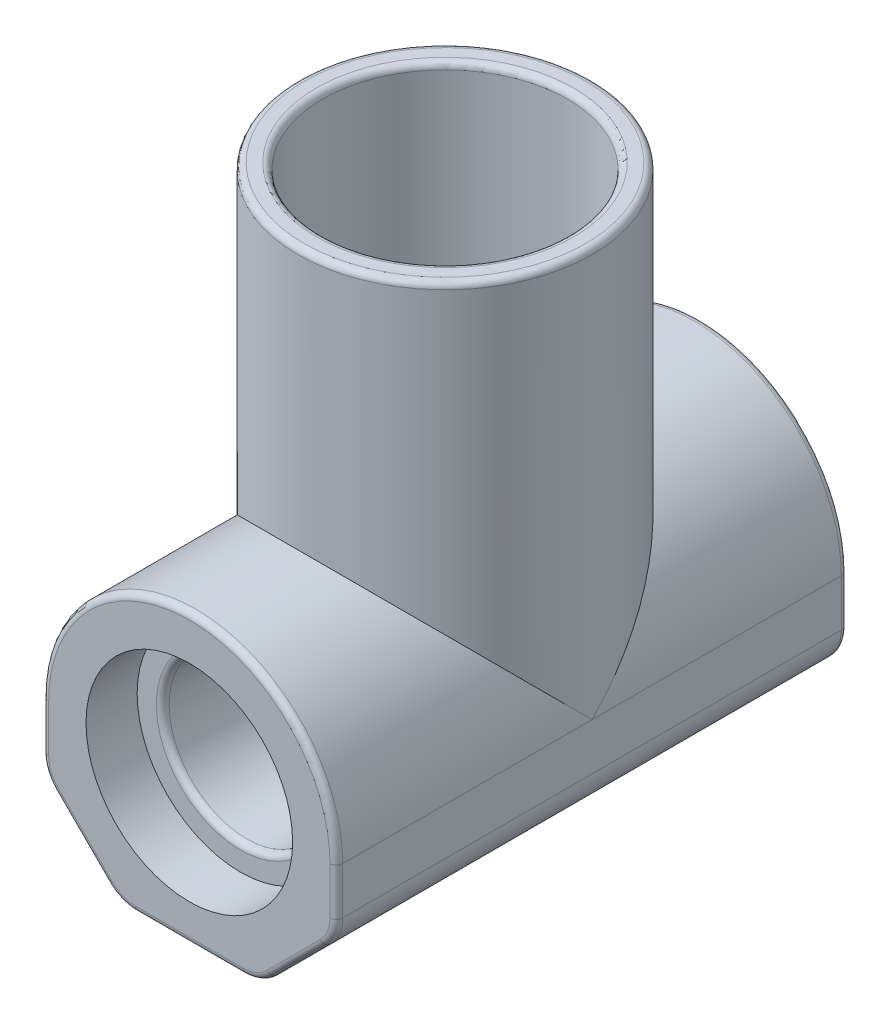
SolidWorks part; units mm, degrees
ref_plane "Front Plane" through (0, 0, 0) normal (0, 0, 1) x (1, 0, 0)
ref_plane "Top Plane" through (0, 0, 0) normal (0, 1, 0) x (1, 0, 0)
ref_plane "Right Plane" through (0, 0, 0) normal (1, 0, 0) x (0, 0, -1)
sketch "Sketch1" plane through (0, 0, 0) normal (0, 0, 1) x (1, 0, 0)
  line L1 (-36.5125, 0) -> (-36.5125, -34.8451)
  line L2 (-36.5125, -34.8451) -> (36.5125, -34.8451)
  line L3 (36.5125, 0) -> (36.5125, -34.8451)
  arc A0 (36.5125, 0) -> (-36.5125, 0) centre (0, 0) ccw
extrude "Boss-Extrude1" add sketch "Sketch1" along normal blind 63.5 and the other way blind 63.5 contours A0 L1 L2 L3
sketch "Sketch3" plane through (0, 0, 0) normal (0, 1, 0) x (1, 0, 0)
  circle A0 centre (0, 0) radius 36.5125
extrude "Boss-Extrude2" add sketch "Sketch3" along normal blind 101.6
sketch "Sketch4" plane through (0, 0, -63.5) normal (0, 0, -1) x (-1, 0, 0)
  circle A0 centre (0, 0) radius 19.304
extrude "Cut-Extrude1" cut sketch "Sketch4" against normal through all
sketch "Sketch5" plane through (0, 0, -63.5) normal (0, 0, -1) x (-1, 0, 0)
  circle A0 centre (0, 0) radius 25.654
extrude "Cut-Extrude2" cut sketch "Sketch5" against normal blind 12.7
sketch "Sketch6" plane through (0, 0, 63.5) normal (0, 0, 1) x (1, 0, 0)
  circle A0 centre (0, 0) radius 25.654
extrude "Cut-Extrude3" cut sketch "Sketch6" against normal blind 12.7
sketch "Sketch7" plane through (0, 101.6, 0) normal (0, 1, 0) x (1, 0, 0)
  circle A0 centre (0, 0) radius 30.4165
extrude "Cut-Extrude4" cut sketch "Sketch7" against normal blind 78.834
chamfer "Chamfer1" distance 19.05 angle 45 2 edges at (36.5125, -34.8451, 0) (-36.5125, -34.8451, 0)
fillet "Fillet1" radius 10 4 edges at (36.5125, -15.7951, 0) (17.4625, -34.8451, 0) (-17.4625, -34.8451, 0) (-36.5125, -15.7951, 0)
fillet "Fillet2" radius 1.5875 24 edges at (36.5125, -5.8265, -63.5) (35.7513, -15.4798, -63.5) (26.9875, -25.3201, -63.5) (17.1472, -34.0839, -63.5) (0, -34.8451, -63.5) (-17.1472, -34.0839, -63.5) (-26.9875, -25.3201, -63.5) (-35.7513, -15.4798, -63.5) (-36.5125, -5.8265, -63.5) (36.5125, -5.8265, 63.5) (35.7513, -15.4798, 63.5) (26.9875, -25.3201, 63.5) (17.1472, -34.0839, 63.5) (0, -34.8451, 63.5) (-17.1472, -34.0839, 63.5) (-26.9875, -25.3201, 63.5) (-35.7513, -15.4798, 63.5) (-36.5125, -5.8265, 63.5) (-19.304, 0, -50.8) (19.304, 0, 50.8) (0, 101.6, 30.4165) (0, 101.6, 36.5125) (0, 36.5125, -63.5) (0, 36.5125, 63.5)
